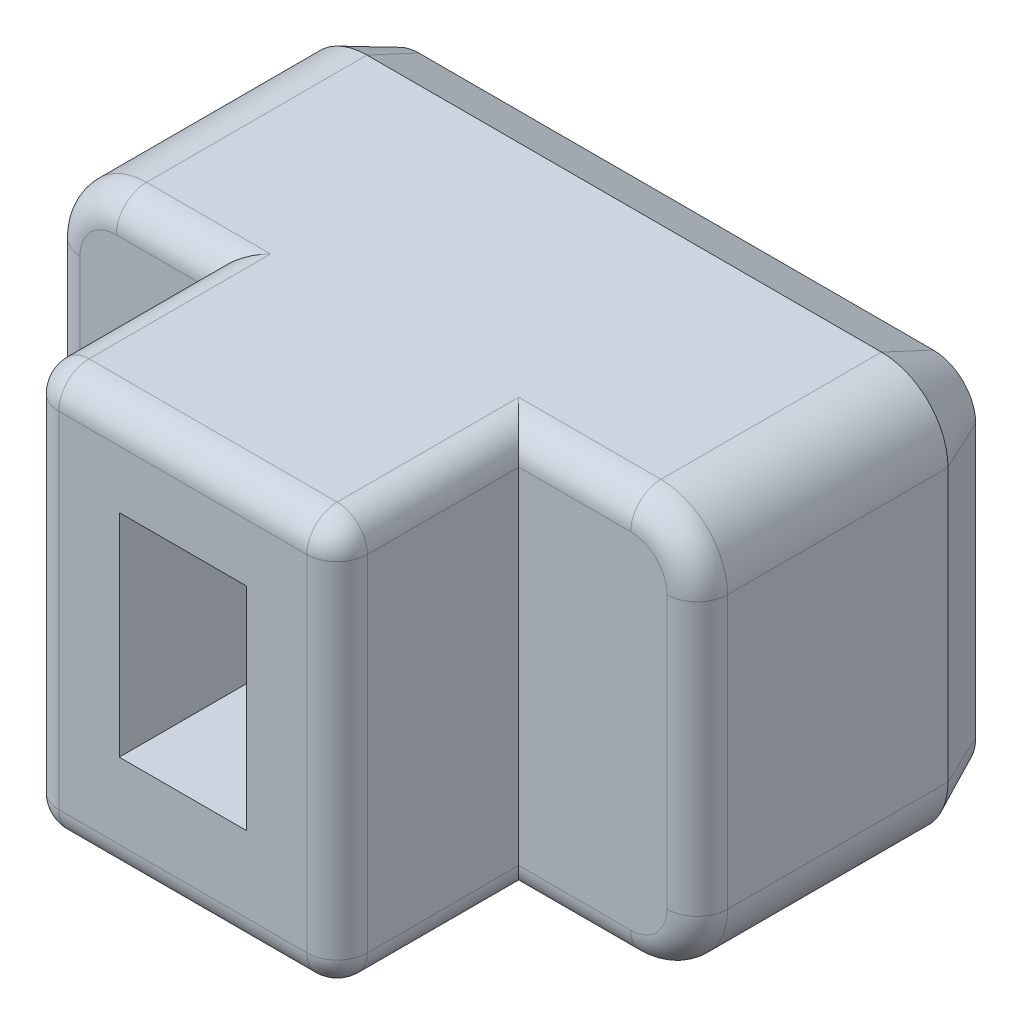
SolidWorks part; units mm, degrees
ref_plane "Plan de face" through (0, 0, 0) normal (0, 0, 1) x (1, 0, 0)
ref_plane "Plan de dessus" through (0, 0, 0) normal (0, 1, 0) x (1, 0, 0)
ref_plane "Plan de droite" through (0, 0, 0) normal (1, 0, 0) x (0, 0, -1)
sketch "Esquisse2" plane through (0, 0, 0) normal (0, 0, 1) x (1, 0, 0)
  line L1 (1.1, 0) -> (9.6, 0)
  line L2 (0, 1.1) -> (0, 5.6)
  line L3 (1.1, 6.7) -> (9.6, 6.7)
  line L4 (10.7, 1.1) -> (10.7, 5.6)
  arc A0 (9.6, 6.7) -> (10.7, 5.6) centre (9.6, 5.6) cw
  arc A1 (9.6, 0) -> (10.7, 1.1) centre (9.6, 1.1) ccw
  arc A2 (1.1, 0) -> (0, 1.1) centre (1.1, 1.1) cw
  arc A3 (0, 5.6) -> (1.1, 6.7) centre (1.1, 5.6) cw
  point P7 (10.7, 6.7)
  point P12 (0, 0)
  point P15 (0, 6.7)
  dimension "D3" = 1.1
  dimension "D1" = 10.7
  dimension "D2" = 6.7
extrude "Boss.-Extru.1" add sketch "Esquisse2" along normal blind 8
sketch "Esquisse3" plane through (0, 0, 8) normal (0, 0, 1) x (1, 0, 0)
  line L0 (0, 5.6) -> (0, 1.1) construction
  line L1 (4.15, 5.25) -> (6.25, 5.25)
  line L2 (4.15, 5.25) -> (4.15, 1.75)
  line L3 (4.15, 1.75) -> (6.25, 1.75)
  line L4 (6.25, 5.25) -> (6.25, 1.75)
  line L5 (10.7, 1.1) -> (10.7, 5.6) construction
  line L6 (9.6, 6.7) -> (1.1, 6.7) construction
  line L7 (1.1, 0) -> (9.6, 0) construction
  dimension "D1" = 2.1
  dimension "D2" = 3.5
  dimension "D3" = 4.15
  dimension "D4" = 4.45
  dimension "D5" = 1.45
  dimension "D6" = 1.75
extrude "Enlèv. mat.-Extru.1" cut sketch "Esquisse3" against normal blind 3
sketch "Esquisse4" plane through (0, 0, 8) normal (0, 0, 1) x (1, 0, 0)
  line L0 (2.65, 6.7) -> (2.65, 0)
  line L1 (9.6, 6.7) -> (1.1, 6.7) construction
  line L2 (1.1, 0) -> (9.6, 0) construction
  line L3 (2.65, 0) -> (7.75, 0)
  line L4 (7.75, 0) -> (7.75, 6.7)
  line L5 (7.75, 6.7) -> (2.65, 6.7)
  line L6 (4.15, 5.25) -> (4.15, 1.75) construction
  line L7 (6.25, 1.75) -> (6.25, 5.25) construction
  dimension "D1" = 1.5
  dimension "D2" = 1.5
extrude "Enlèv. mat.-Extru.2" cut sketch "Esquisse4" against normal blind 3 flip side to cut
fillet "Congé1" radius 0.5 18 edges at (8.675, 0, 5) (10.3778, 0.3222, 5) (10.7, 3.35, 5) (10.3778, 6.3778, 5) (1.875, 6.7, 5) (0.3222, 6.3778, 5) (1.875, 0, 5) (0.3222, 0.3222, 5) (7.75, 6.7, 6.5) (2.65, 6.7, 6.5) (7.75, 0, 6.5) (2.65, 0, 6.5) (2.65, 3.35, 8) (5.2, 6.7, 8) (7.75, 3.35, 8) (5.2, 0, 8) (8.675, 6.7, 5) (0, 3.35, 5)
chamfer "Chanfrein1" distance 0.4 angle 65 8 edges at (5.35, 0, 0) (10.3778, 0.3222, 0) (0.3222, 0.3222, 0) (10.7, 3.35, 0) (0, 3.35, 0) (10.3778, 6.3778, 0) (0.3222, 6.3778, 0) (5.35, 6.7, 0) first distance on face at (5.35, 3.35, 0)
sketch "Esquisse5" plane through (0, 0, 0) normal (0, 0, 1) x (1, 0, 0)
  line L0 (-0.9378, 5.093) -> (11.6517, 5.093) construction
  text T0 "ENT" font "Corbel" height 3.5
extrude "Enlèv. mat.-Extru.3" cut sketch "Esquisse5" along normal blind 0.2
extrude "Boss.-Extru.2" add sketch "Esquisse5<4>" against normal blind 0.2
sketch "Esquisse5<4>" plane through (0, 0, 0) normal (0, 0, 1) x (1, 0, 0) same geometry as "Esquisse5"
